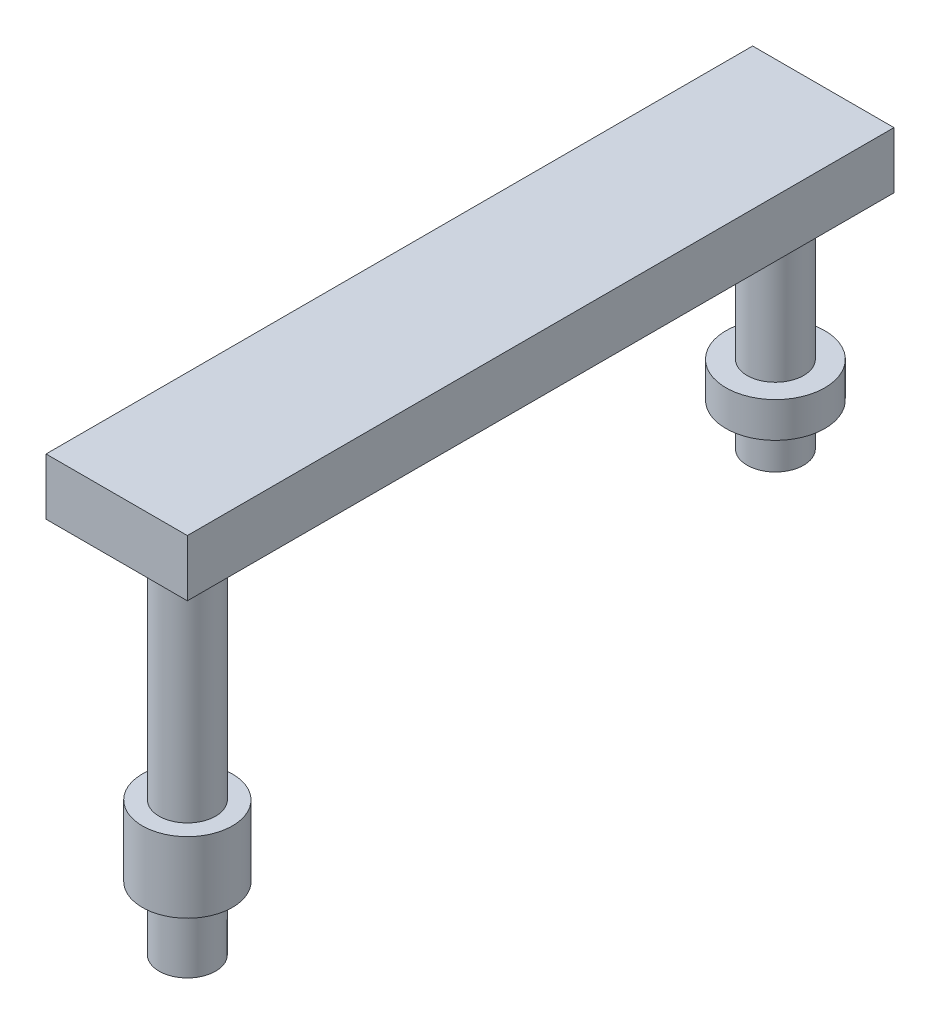
SolidWorks part; units mm, degrees
ref_plane "Front Plane" through (0, 0, 0) normal (0, 0, 1) x (1, 0, 0)
ref_plane "Top Plane" through (0, 0, 0) normal (0, 1, 0) x (1, 0, 0)
ref_plane "Right Plane" through (0, 0, 0) normal (1, 0, 0) x (0, 0, -1)
sketch "Sketch2" plane through (0, 0, 0) normal (0, 1, 0) x (-1, 0, 0)
  circle A0 centre (0, 0) radius 5.08
  dimension "D1" = 10.16
extrude "Boss-Extrude2" add sketch "Sketch2" along normal blind 41.91
sketch "Sketch3" plane through (0, 0, 0) normal (0, 0, 1) x (1, 0, 0)
  line L1 (0, 0) -> (0, 7.62) construction
  line L4 (0, 7.62) -> (0, 13.97)
  line L7 (0, 7.62) -> (-8.89, 7.62)
  line L8 (-8.89, 7.62) -> (-8.89, 13.97)
  line L9 (-8.89, 13.97) -> (0, 13.97)
  dimension "D1" = 6.35
  dimension "D2" = 8.89
  dimension "D3" = 7.62
revolve "Revolve1" add sketch "Sketch3" angle 360 about L1
sketch "Sketch7" plane through (0, 0, 0) normal (0, -1, 0) x (1, 0, 0)
  line L0 (0.577, -2.5995) -> (2.6291, -0.2454)
  circle A1 centre (-1.9453, 1.6968) radius 0.0101
  circle A3 centre (-0.0417, 0.0113) radius 2.6831
  point P7 (2.6291, -0.2454)
extrude "Cut-Extrude2" cut sketch "Sketch7" against normal blind 20.32 contours L0 A3 A1 region at (-0.1304, 0, 0.0886)
sketch "Sketch8" plane through (0, 41.91, 0) normal (0, 1, 0) x (1, 0, 0)
  line L1 (-12.7, 8.6111) -> (12.7, 8.6111)
  line L2 (-12.7, 8.6111) -> (-12.7, -118.3889)
  line L3 (-12.7, -118.3889) -> (12.7, -118.3889)
  line L4 (12.7, 8.6111) -> (12.7, -118.3889)
  point P4 (0, 8.6111)
  dimension "D1" = 25.4
  dimension "D2" = 127
extrude "Boss-Extrude3" add sketch "Sketch8" along normal blind 10.16
sketch "Sketch9" plane through (0, 41.91, 0) normal (0, -1, 0) x (1, 0, 0)
  line L0 (-12.7, 118.3889) -> (12.7, 118.3889) construction
  line L1 (0.8133, 103.1405) -> (2.6638, 105.9336)
  circle A0 centre (0, 105.6889) radius 5.08
  circle A1 centre (-1.6961, 107.3391) radius 0.0101
  circle A3 centre (0, 105.6889) radius 2.675
  point P2 (0, 0)
  point P4 (0, 107.8338)
  point P7 (0, 0)
  point P14 (0, 0)
  dimension "D1" = 10.16
  dimension "D3" = 5.35
  dimension "D2" = 12.7
extrude "Boss-Extrude4" add sketch "Sketch9" along normal blind 67.818 contours A0 A3 | L1 A3 region at (1.9371, 41.91, 104.4055) region at (-4.9363, 41.91, 105.6889)
sketch "Sketch10" plane through (0, -25.908, 0) normal (0, -1, 0) x (1, 0, 0)
  circle A0 centre (0, 105.6889) radius 8.0936
extrude "Boss-Extrude5" add sketch "Sketch10" against normal blind 12.7 from offset 11.43 offset against normal yes
